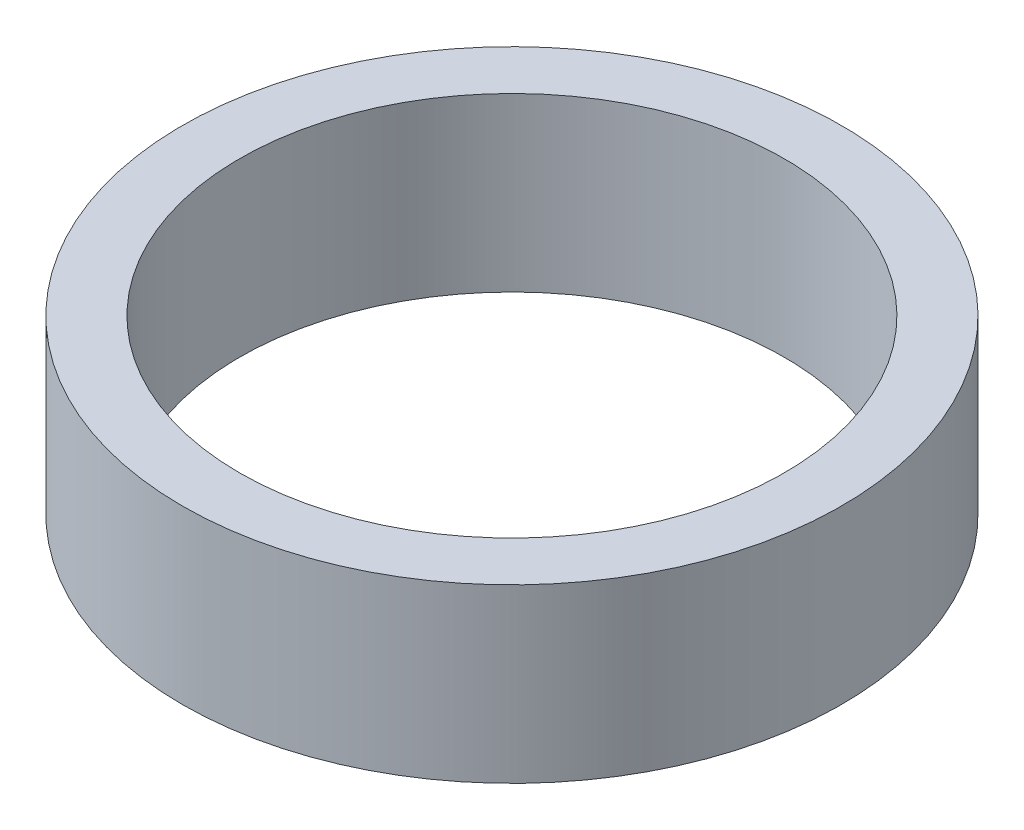
SolidWorks part; units mm, degrees
ref_plane "Front Plane" through (0, 0, 0) normal (0, 0, 1) x (1, 0, 0)
ref_plane "Top Plane" through (0, 0, 0) normal (0, 1, 0) x (1, 0, 0)
ref_plane "Right Plane" through (0, 0, 0) normal (1, 0, 0) x (0, 0, -1)
sketch "Sketch1" plane through (0, 0, 0) normal (0, 1, 0) x (1, 0, 0)
  circle A0 centre (0, 0) radius 57.5
  dimension "FLANGE_OD" = 115
extrude "Boss-Extrude1" add sketch "Sketch1" along normal blind 30
sketch "Sketch2" plane through (0, 0, 0) normal (0, 1, 0) x (1, 0, 0)
  circle A0 centre (0, 0) radius 47.5
  dimension "BORE_D" = 95
extrude "Cut-Extrude1" cut sketch "Sketch2" along normal through all
sketch "Sketch3" plane through (0, 30, 0) normal (0, 1, 0) x (1, 0, 0)
  circle A0 centre (0, 0) radius 26.0496 construction
  circle A1 centre (-26.0496, 0) radius 1.7247
  dimension "BOLT_D" = 3.4494
  dimension "BOLT_PCD" = 52.0992
extrude "Cut-Extrude2" cut sketch "Sketch3" against normal blind 18.7957 rebuild error yes
pattern_circular "CirPattern1" count 6 over 360 rebuild error yes
